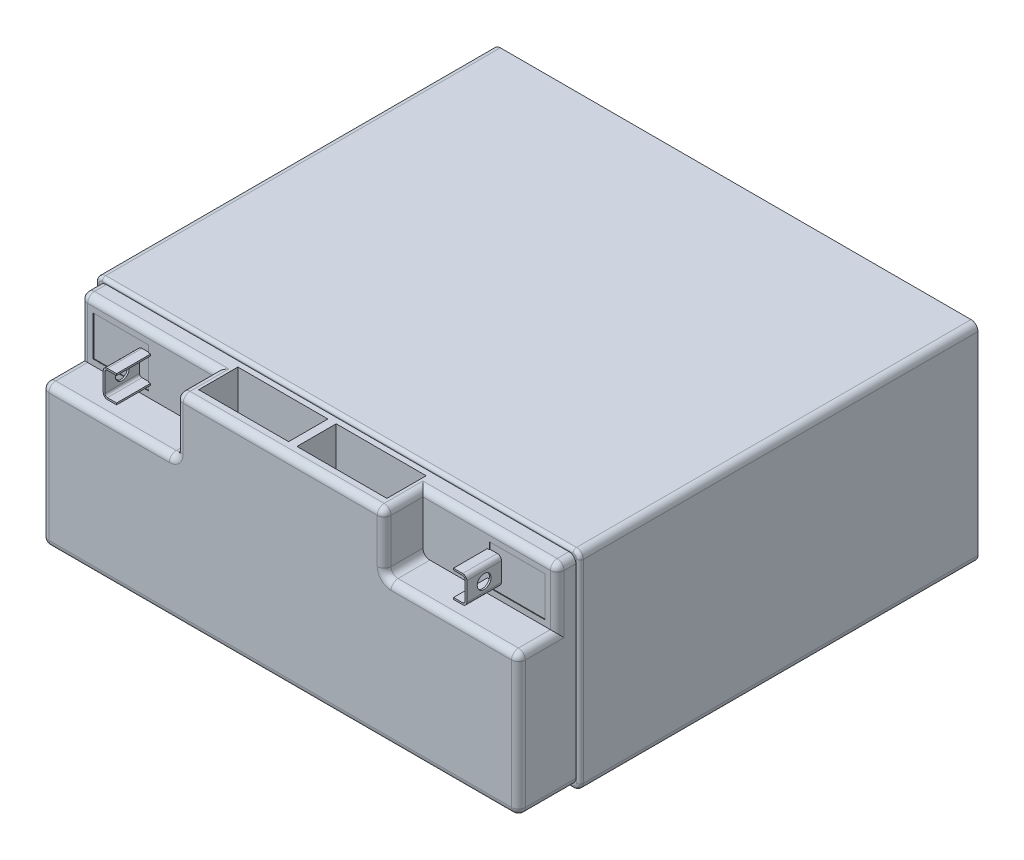
SolidWorks part; units mm, degrees
material "Melamine resin"
ref_plane "Front Plane" through (0, 0, 0) normal (0, 0, 1) x (1, 0, 0)
ref_plane "Top Plane" through (0, 0, 0) normal (0, 1, 0) x (1, 0, 0)
ref_plane "Right Plane" through (0, 0, 0) normal (1, 0, 0) x (0, 0, -1)
ref_plane "Plane1" through (0, -62.2132, 0) normal (0, -1, 0) x (1, 0, 0)
sketch "Sketch1" plane through (0, -62.2132, 0) normal (0, -1, 0) x (1, 0, 0)
  line L0 (-33.1131, 0) -> (144.6869, 0)
  line L1 (144.6869, 0) -> (144.6869, 146.05)
  line L2 (144.6869, 146.05) -> (-33.1131, 146.05)
  line L3 (-33.1131, 146.05) -> (-33.1131, 0)
  dimension "D1" = 177.8
  dimension "D2" = 146.05
extrude "Extrude1" add sketch "Sketch1" against normal blind 76.2
sketch "Sketch2" plane through (0, 0, 146.05) normal (0, 0, 1) x (1, 0, 0)
  line L0 (143.2096, 12.5094) -> (143.2096, -60.7358)
  line L1 (143.2096, -60.7358) -> (-31.6357, -60.7358)
  line L2 (-31.6357, -60.7358) -> (-31.6357, 12.5094)
  line L3 (-31.6357, 12.5094) -> (143.2096, 12.5094)
  line L4 (-33.1131, 13.9868) -> (-33.1131, -62.2132) construction
  line L5 (144.6869, -62.2132) -> (-33.1131, -62.2132) construction
  dimension "D1" = 1.4774
  dimension "D2" = 176.3226
  dimension "D3" = 1.4774
  dimension "D4" = 74.7226
extrude "Extrude2" add sketch "Sketch2" along normal blind 21.082
sketch "Sketch3" plane through (-31.6357, 0, 0) normal (-1, 0, 0) x (0, 0, 1)
  line L0 (152.908, 12.5094) -> (152.908, -8.8266)
  line L1 (152.908, -8.8266) -> (167.132, -8.8266)
  line L2 (167.132, -8.8266) -> (167.132, 12.5094)
  line L3 (167.132, 12.5094) -> (152.908, 12.5094)
  line L4 (167.132, 12.5094) -> (167.132, -60.7358) construction
  line L5 (167.132, -60.7358) -> (146.05, -60.7358) construction
  dimension "D1" = 14.224
  dimension "D2" = 51.9092
  dimension "D3" = 73.2452
extrude "Extrude3" cut sketch "Sketch3" against normal blind 49.276
sketch "Sketch4" plane through (0, 0, 152.908) normal (0, 0, 1) x (1, 0, 0)
  line L0 (-27.0726, 7.9428) -> (-27.0726, -6.6776)
  line L1 (-27.0726, -6.6776) -> (-6.7872, -6.6776)
  line L2 (-6.7872, -6.6776) -> (-6.7872, -4.5374)
  line L3 (-6.7872, -4.5374) -> (-10.918, -4.5374)
  line L4 (-10.918, -4.5374) -> (-10.918, 5.3949)
  line L5 (-10.918, 5.3949) -> (-6.7872, 5.3949)
  line L6 (-6.7872, 5.3949) -> (-6.7872, 7.9428)
  line L7 (-6.7872, 7.9428) -> (-27.0726, 7.9428)
  line L8 (-31.6357, 12.5094) -> (-31.6357, -8.8266) construction
  line L9 (17.6403, -8.8266) -> (-31.6357, -8.8266) construction
  dimension "D1" = 4.5631
  dimension "D2" = 20.7177
  dimension "D3" = 24.8485
  dimension "D4" = 2.149
  dimension "D5" = 4.2892
  dimension "D6" = 14.2215
  dimension "D7" = 16.7694
extrude "Extrude4" cut sketch "Sketch4" against normal blind 0.254
sketch "Sketch5" plane through (0, 0, 152.908) normal (0, 0, 1) x (1, 0, 0)
  line L0 (-6.018, -4.5374) -> (-10.918, -4.5374)
  line L1 (-10.918, -4.5374) -> (-10.918, 5.3949)
  line L2 (-10.918, 5.3949) -> (-6.018, 5.3949)
  line L3 (-6.018, 5.3949) -> (-6.018, -4.5374)
  line L4 (-31.6357, 12.5094) -> (-31.6357, -8.8266) construction
  line L5 (17.6403, -8.8266) -> (-31.6357, -8.8266) construction
  dimension "D1" = 20.7177
  dimension "D2" = 25.6177
  dimension "D3" = 4.2892
  dimension "D4" = 14.2215
extrude "Extrude5" add sketch "Sketch5" along normal blind 12.446
sketch "Sketch6" plane through (-6.018, 0, 0) normal (1, 0, 0) x (0, 0, -1)
  line L0 (-152.908, -3.9265) -> (-152.908, 4.784)
  line L1 (-152.908, 4.784) -> (-165.354, 4.784)
  line L2 (-165.354, 4.784) -> (-165.354, -3.9265)
  line L3 (-165.354, -3.9265) -> (-152.908, -3.9265)
  line L4 (-165.354, -4.5374) -> (-165.354, 5.3949) construction
  line L5 (-165.354, -4.5374) -> (-152.908, -4.5374) construction
  dimension "D1" = 12.446
  dimension "D2" = 0.6109
  dimension "D3" = 9.3214
extrude "Extrude6" cut sketch "Sketch6" against normal blind 4.289
sketch "Sketch7" plane through (0, 0, 152.908) normal (0, 0, 1) x (1, 0, 0)
  line L0 (-10.3071, 4.784) -> (-10.3071, -3.9265)
  line L1 (-10.3071, -3.9265) -> (-6.7872, -3.9265)
  line L2 (-6.7872, -3.9265) -> (-6.7872, 4.784)
  line L3 (-6.7872, 4.784) -> (-10.3071, 4.784)
  line L4 (-31.6357, 12.5094) -> (-31.6357, -8.8266) construction
  line L5 (17.6403, -8.8266) -> (-31.6357, -8.8266) construction
  dimension "D1" = 21.3286
  dimension "D2" = 24.8485
  dimension "D3" = 4.9001
  dimension "D4" = 13.6106
extrude "Extrude7" cut sketch "Sketch7" against normal blind 0.254
sketch "Sketch8" plane through (0, 12.5094, 0) normal (0, 1, 0) x (-1, 0, 0)
  line L0 (-143.2096, 152.908) -> (-93.9336, 152.908)
  line L1 (-93.9336, 152.908) -> (-93.9336, 167.132)
  line L2 (-93.9336, 167.132) -> (-143.2096, 167.132)
  line L3 (-143.2096, 167.132) -> (-143.2096, 152.908)
  line L4 (31.6357, 152.908) -> (31.6357, 146.05) construction
  line L5 (-143.2096, 146.05) -> (31.6357, 146.05) construction
  dimension "D1" = 125.5692
  dimension "D2" = 174.8452
  dimension "D3" = 6.858
  dimension "D4" = 21.082
extrude "Extrude8" cut sketch "Sketch8" against normal blind 21.336
sketch "Sketch9" plane through (0, 0, 152.908) normal (0, 0, 1) x (1, 0, 0)
  line L0 (118.361, 5.3949) -> (122.4919, 5.3949)
  line L1 (122.4919, 5.3949) -> (122.4919, -4.5374)
  line L2 (122.4919, -4.5374) -> (118.361, -4.5374)
  line L3 (118.361, -4.5374) -> (118.361, -6.6776)
  line L4 (118.361, -6.6776) -> (138.6465, -6.6776)
  line L5 (138.6465, -6.6776) -> (138.6465, 7.9428)
  line L6 (138.6465, 7.9428) -> (118.361, 7.9428)
  line L7 (118.361, 7.9428) -> (118.361, 5.3949)
  line L8 (93.9336, -8.8266) -> (93.9336, 12.5094) construction
  line L9 (143.2096, -8.8266) -> (93.9336, -8.8266) construction
  dimension "D1" = 24.4275
  dimension "D2" = 28.5583
  dimension "D3" = 44.7129
  dimension "D4" = 2.149
  dimension "D5" = 4.2892
  dimension "D6" = 14.2215
  dimension "D7" = 16.7694
extrude "Extrude9" cut sketch "Sketch9" against normal blind 0.254
sketch "Sketch10" plane through (0, 0, 152.908) normal (0, 0, 1) x (1, 0, 0)
  line L0 (122.4919, -4.5374) -> (117.5919, -4.5374)
  line L1 (117.5919, -4.5374) -> (117.5919, 5.3949)
  line L2 (117.5919, 5.3949) -> (122.4919, 5.3949)
  line L3 (122.4919, 5.3949) -> (122.4919, -4.5374)
  line L4 (93.9336, -8.8266) -> (93.9336, 12.5094) construction
  line L5 (143.2096, -8.8266) -> (93.9336, -8.8266) construction
  dimension "D1" = 23.6583
  dimension "D2" = 28.5583
  dimension "D3" = 4.2892
  dimension "D4" = 14.2215
extrude "Extrude10" add sketch "Sketch10" along normal blind 12.446
sketch "Sketch11" plane through (117.5919, 0, 0) normal (-1, 0, 0) x (0, 0, 1)
  line L0 (152.908, 4.784) -> (152.908, -3.9265)
  line L1 (152.908, -3.9265) -> (165.354, -3.9265)
  line L2 (165.354, -3.9265) -> (165.354, 4.784)
  line L3 (165.354, 4.784) -> (152.908, 4.784)
  line L4 (165.354, 5.3949) -> (165.354, -4.5374) construction
  line L5 (165.354, -4.5374) -> (152.908, -4.5374) construction
  dimension "D1" = 12.446
  dimension "D2" = 0.6109
  dimension "D3" = 9.3214
extrude "Extrude11" cut sketch "Sketch11" against normal blind 4.289
sketch "Sketch12" plane through (0, 0, 152.908) normal (0, 0, 1) x (1, 0, 0)
  line L0 (121.8809, 4.784) -> (118.361, 4.784)
  line L1 (118.361, 4.784) -> (118.361, -3.9265)
  line L2 (118.361, -3.9265) -> (121.8809, -3.9265)
  line L3 (121.8809, -3.9265) -> (121.8809, 4.784)
  line L4 (93.9336, -8.8266) -> (93.9336, 12.5094) construction
  line L5 (143.2096, -8.8266) -> (93.9336, -8.8266) construction
  dimension "D1" = 24.4275
  dimension "D2" = 27.9474
  dimension "D3" = 4.9001
  dimension "D4" = 13.6106
extrude "Extrude12" cut sketch "Sketch12" against normal blind 0.254
sketch "Sketch13" plane through (0, 12.5094, 0) normal (0, 1, 0) x (-1, 0, 0)
  line L0 (-90.3309, 148.1138) -> (-57.3109, 148.1138)
  line L1 (-57.3109, 148.1138) -> (-57.3109, 162.5135)
  line L2 (-57.3109, 162.5135) -> (-90.3309, 162.5135)
  line L3 (-90.3309, 162.5135) -> (-90.3309, 148.1138)
  line L4 (31.6357, 152.908) -> (31.6357, 146.05) construction
  line L5 (-143.2096, 146.05) -> (31.6357, 146.05) construction
  dimension "D1" = 88.9466
  dimension "D2" = 121.9666
  dimension "D3" = 2.0638
  dimension "D4" = 16.4635
extrude "Extrude13" cut sketch "Sketch13" against normal blind 19.05
sketch "Sketch14" plane through (0, 12.5094, 0) normal (0, 1, 0) x (-1, 0, 0)
  line L0 (-54.2629, 148.1138) -> (-21.2429, 148.1138)
  line L1 (-21.2429, 148.1138) -> (-21.2429, 162.5135)
  line L2 (-21.2429, 162.5135) -> (-54.2629, 162.5135)
  line L3 (-54.2629, 162.5135) -> (-54.2629, 148.1138)
  line L4 (31.6357, 152.908) -> (31.6357, 146.05) construction
  line L5 (-143.2096, 146.05) -> (31.6357, 146.05) construction
  dimension "D1" = 52.8786
  dimension "D2" = 85.8986
  dimension "D3" = 2.0638
  dimension "D4" = 16.4635
extrude "Extrude14" cut sketch "Sketch14" against normal blind 19.05
sketch "Sketch15" plane through (0, -60.7358, 0) normal (0, -1, 0) x (1, 0, 0)
  line L0 (56.8496, 162.8434) -> (56.8496, 147.6421)
  line L1 (56.8496, 147.6421) -> (120.3496, 147.6421)
  line L2 (120.3496, 147.6421) -> (120.3496, 162.8434)
  line L3 (120.3496, 162.8434) -> (56.8496, 162.8434)
  line L4 (-31.6357, 167.132) -> (-31.6357, 146.05) construction
  line L5 (-31.6357, 167.132) -> (143.2096, 167.132) construction
  dimension "D1" = 88.4852
  dimension "D2" = 151.9852
  dimension "D3" = 4.2886
  dimension "D4" = 19.4899
extrude "Extrude15" cut sketch "Sketch15" against normal blind 19.558
sketch "Sketch16" plane through (0, -60.7358, 0) normal (0, -1, 0) x (1, 0, 0)
  line L0 (-8.7757, 162.8434) -> (-8.7757, 147.6421)
  line L1 (-8.7757, 147.6421) -> (54.7243, 147.6421)
  line L2 (54.7243, 147.6421) -> (54.7243, 162.8434)
  line L3 (54.7243, 162.8434) -> (-8.7757, 162.8434)
  line L4 (-31.6357, 167.132) -> (-31.6357, 146.05) construction
  line L5 (-31.6357, 167.132) -> (143.2096, 167.132) construction
  dimension "D1" = 22.86
  dimension "D2" = 86.36
  dimension "D3" = 4.2886
  dimension "D4" = 19.4899
extrude "Extrude16" cut sketch "Sketch16" against normal blind 19.558
hole_wizard "Hole1" positions "Sketch18" profile "Sketch17" legacy
sketch "Sketch18" plane through (122.4919, 0, 0) normal (1, 0, 0) x (0, 0, -1)
  point P0 (-159.004, 0.4288)
sketch "Sketch17" plane through (122.4919, 0.4288, 159.004) normal (0, 1, 0) x (0, 0, -1)
  line L0 (0, 0) -> (0, 0.6109)
  line L1 (0, 0.6109) -> (2.54, 0.6109)
  line L2 (2.54, 0.6109) -> (2.54, 0)
  line L3 (2.54, 0) -> (0, 0)
  line L4 (0, 110) -> (0, -10) construction
  dimension "Diameter" = 5.08
  dimension "Depth" = 0.6109
hole_wizard "Hole2" positions "Sketch20" profile "Sketch19" legacy
sketch "Sketch20" plane through (-10.3071, 0, 0) normal (1, 0, 0) x (0, 0, -1)
  point P0 (-159.004, 0.4288)
sketch "Sketch19" plane through (-10.3071, 0.4288, 159.004) normal (0, 1, 0) x (0, 0, -1)
  line L0 (0, 0) -> (0, 22.806)
  line L1 (0, 22.806) -> (2.54, 22.806)
  line L2 (2.54, 22.806) -> (2.54, 0)
  line L3 (2.54, 0) -> (0, 0)
  line L4 (0, 110) -> (0, -10) construction
  dimension "Diameter" = 5.08
  dimension "Depth" = 22.806
fillet "Fillet1" radius 2.54 1 edges at (144.6869, 13.9868, 73.025) tangent propagation no
fillet "Fillet2" radius 2.54 1 edges at (-33.1131, -62.2132, 73.025) tangent propagation no
fillet "Fillet3" radius 2.54 1 edges at (144.6869, -62.2132, 73.025) tangent propagation no
fillet "Fillet4" radius 2.54 1 edges at (93.9336, -8.8266, 160.02) tangent propagation no
fillet "Fillet5" radius 2.54 1 edges at (-33.1131, 13.9868, 73.025) tangent propagation no
fillet "Fillet6" radius 2.54 1 edges at (17.6403, -8.8266, 160.02) tangent propagation no
fillet "Fillet7" radius 0.9131 1 edges at (-10.3071, -3.9265, 159.004) tangent propagation no
fillet "Fillet8" radius 0.9131 1 edges at (121.8809, 4.784, 159.004) tangent propagation no
fillet "Fillet9" radius 0.9131 1 edges at (-10.3071, 4.784, 159.004) tangent propagation no
fillet "Fillet10" radius 0.9131 1 edges at (121.8809, -3.9265, 159.004) tangent propagation no
fillet "Fillet11" radius 1.27 8 edges at (143.943, 13.2428, 146.05) (55.7869, 13.9868, 146.05) (144.6869, -24.1132, 146.05) (-32.3691, 13.2428, 146.05) (143.943, -61.4693, 146.05) (-33.1131, -24.1132, 146.05) (55.7869, -62.2132, 146.05) (-32.3691, -61.4693, 146.05) tangent propagation no
fillet "Fillet12" radius 1.524 1 edges at (-10.918, 5.3949, 159.004) tangent propagation no
fillet "Fillet13" radius 1.524 1 edges at (122.4919, -4.5374, 159.004) tangent propagation no
fillet "Fillet14" radius 1.524 1 edges at (-10.918, -4.5374, 159.004) tangent propagation no
fillet "Fillet15" radius 1.524 1 edges at (122.4919, 5.3949, 159.004) tangent propagation no
fillet "Fillet16" radius 2.54 22 edges at (143.2096, -60.7358, 156.5802) (143.2096, 12.5094, 149.4682) (143.2096, 1.8414, 152.908) (-31.6357, -60.7358, 156.5802) (55.7869, -60.7358, 167.132) (143.2096, -34.7812, 167.132) (143.2096, -8.8266, 160.02) (118.5716, 12.5094, 152.908) (-31.6357, 12.5094, 149.4682) (-31.6357, 1.8414, 152.908) (-31.6357, -8.8266, 160.02) (-31.6357, -34.7812, 167.132) (93.9336, 3.1114, 167.132) (119.8416, -8.8266, 167.132) (94.6775, -8.0826, 167.132) (93.9336, 12.5094, 160.02) (-6.9977, 12.5094, 152.908) (17.6403, 3.1114, 167.132) (-8.2677, -8.8266, 167.132) (16.8964, -8.0826, 167.132) (55.7869, 12.5094, 167.132) (17.6403, 12.5094, 160.02)
